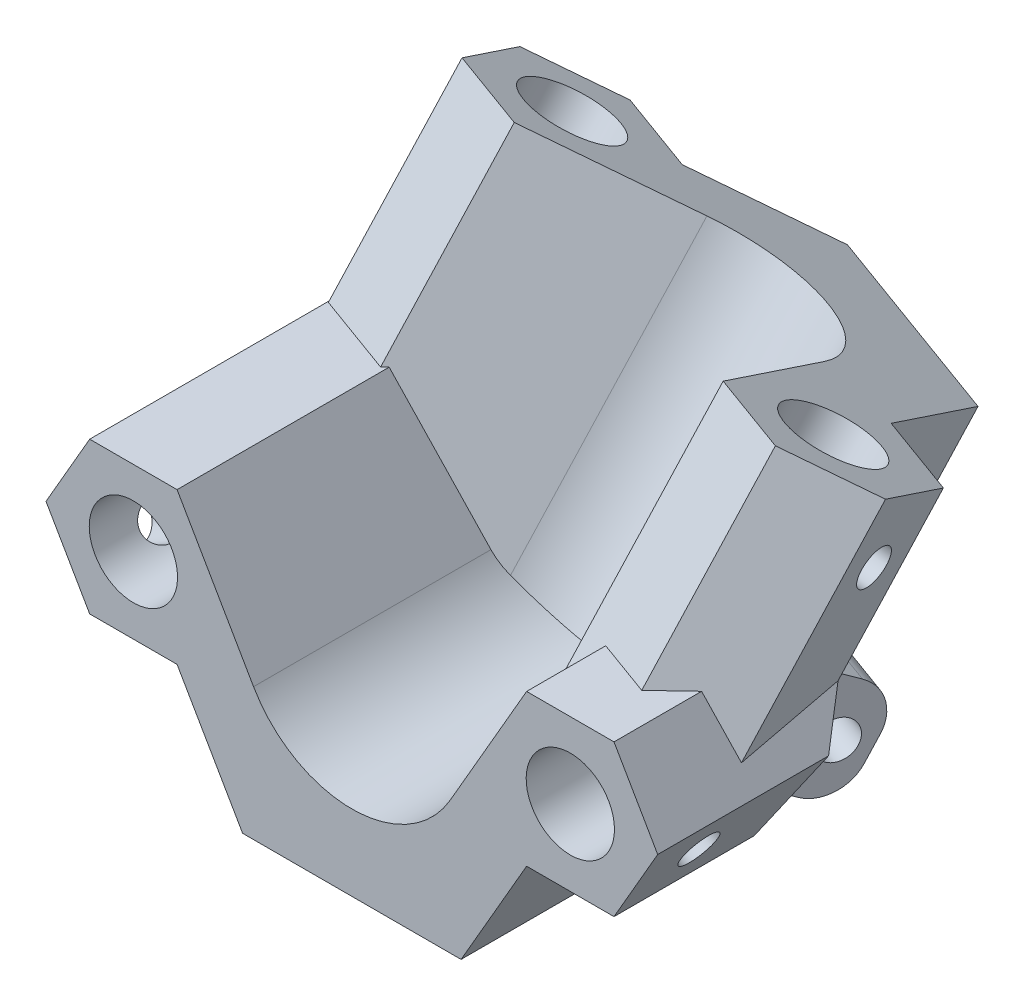
SolidWorks part; units mm, degrees
ref_plane "Front Plane" through (0, 0, 0) normal (0, 0, 1) x (1, 0, 0)
ref_plane "Top Plane" through (0, 0, 0) normal (0, 1, 0) x (1, 0, 0)
ref_plane "Right Plane" through (0, 0, 0) normal (1, 0, 0) x (0, 0, -1)
sketch "Sketch2" plane through (0, 0, 0) normal (0, 1, 0) x (1, 0, 0)
  line L0 (0, 0) -> (0, -10) construction
  line L1 (0, 0) -> (3.4202, 9.3969) construction
  dimension "D1" = 10
  dimension "D2" = 10
  dimension "D3" = 160
ref_plane "Plane1" through (0, 0, 0) normal (0.9397, 0, 0.342) x (0.342, 0, -0.9397)
sketch "Sketch3" plane through (0, 0, 0) normal (0.9397, 0, 0.342) x (0.342, 0, -0.9397)
  line L0 (0, 0) -> (10, 17.3205) construction
  line L1 (10, 17.3205) -> (10, 0) construction
  line L2 (10, 0) -> (0, 0) construction
  dimension "D1" = 30
  dimension "D2" = 10
sketch "Sketch5" plane through (0, 0, 0) normal (0, 0, 1) x (1, 0, 0)
  line L0 (0, 0) -> (10.3923, 0) construction
  line L1 (15.5705, 3.0311) -> (8.6603, 15)
  line L2 (8.6603, 15) -> (-8.6603, 15)
  line L3 (-8.6603, 15) -> (-13.8564, 6)
  line L4 (-13.8564, -6) -> (-8.6603, -15)
  line L5 (-8.6603, -15) -> (8.6603, -15)
  line L6 (8.6603, -15) -> (13.8564, -6)
  line L7 (0, -55) -> (0, 55) construction
  line L8 (24.2487, 0) -> (20.7846, 6)
  line L9 (20.7846, 6) -> (13.8564, 6)
  line L10 (13.8564, 6) -> (7.7942, -4.5)
  line L11 (10.3923, 0) -> (7.7942, 4.5) construction
  line L12 (13.8564, -6) -> (20.7846, -6)
  line L13 (20.7846, -6) -> (24.2487, 0)
  line L14 (-20.7846, -6) -> (-24.2487, 0)
  line L15 (-13.8564, -6) -> (-20.7846, -6)
  line L16 (-7.7942, 4.5) -> (-13.8564, -6) construction
  line L17 (-13.8564, 6) -> (-7.7942, -4.5)
  line L18 (-20.7846, 6) -> (-13.8564, 6)
  line L19 (-24.2487, 0) -> (-20.7846, 6)
  line L20 (-13.8564, 6) -> (-15.5705, 3.0311) construction
  line L21 (-15.5705, 3.0311) -> (-17.3205, 0) construction
  line L22 (-17.3205, 0) -> (-15.5705, -3.0311) construction
  line L23 (-15.5705, -3.0311) -> (-13.8564, -6) construction
  line L24 (-7.7942, -4.5) -> (-10.3923, 0) construction
  line L25 (-10.3923, 0) -> (-7.7942, 4.5) construction
  line L26 (12.1244, -3) -> (13.8564, -6) construction
  line L27 (13.8564, -6) -> (14.3205, -5.1962) construction
  line L28 (15.5705, -3.0311) -> (17.3205, 0) construction
  line L29 (14.3205, -5.1962) -> (15.5705, -3.0311) construction
  line L30 (7.7942, 4.5) -> (12.1244, -3) construction
  line L31 (7.7942, -4.5) -> (10.3923, 0) construction
  line L32 (10.3923, 0) -> (9, 0) construction
  line L33 (9, 0) -> (15, 0) construction
  line L34 (15, 0) -> (17.3205, 0) construction
  line L35 (17.3205, 0) -> (15.5705, 3.0311) construction
  circle A0 centre (0, 0) radius 15 construction
  arc A1 (-7.7942, -4.5) -> (7.7942, -4.5) centre (0, 0) ccw
  circle A2 centre (17.3205, 0) radius 6 construction
  circle A3 centre (17.3205, 0) radius 3.5
  circle A4 centre (-17.3205, 0) radius 3.5
  arc A5 (7.7942, -4.5) -> (-7.7942, -4.5) centre (0, 0) ccw construction
  dimension "D2" = 18
  dimension "D4" = 7
  dimension "D1" = 30
  dimension "D3" = 12
extrude "Boss-Extrude2" add sketch "Sketch5" along normal blind 15 contours A4 | L17 A1 L10 L9 L8 L13 L12 L6 L5 L4 L15 L14 L19 L18 | A3
ref_plane "Plane2" through (3.4202, 17.3205, -9.3969) normal (0.171, 0.866, -0.4698) x (0.9853, -0.1503, 0.0815)
sketch "Sketch10" plane through (0, 0, 0) normal (0, 0, -1) x (-1, 0, 0)
  line L0 (-7.7942, -4.5) -> (-13.8564, 6)
  line L1 (-13.8564, 6) -> (-20.7846, 6)
  line L2 (-20.7846, 6) -> (-24.2487, 0)
  line L3 (-24.2487, 0) -> (-20.7846, -6)
  line L4 (-20.7846, -6) -> (-13.8564, -6)
  line L5 (-13.8564, -6) -> (-8.6603, -15)
  line L6 (-8.6603, -15) -> (8.6603, -15)
  line L7 (8.6603, -15) -> (13.8564, -6)
  line L8 (13.8564, -6) -> (20.7846, -6)
  line L9 (20.7846, -6) -> (24.2487, 0)
  line L10 (24.2487, 0) -> (20.7846, 6)
  line L11 (20.7846, 6) -> (13.8564, 6)
  line L12 (20.7846, 6) -> (13.8564, 6) construction
  line L13 (13.8564, 6) -> (7.7942, -4.5)
  arc A0 (-7.7942, -4.5) -> (7.7942, -4.5) centre (0, 0) ccw
  arc A1 (-7.7942, -4.5) -> (7.7942, -4.5) centre (0, 0) ccw construction
  arc A2 (7.7942, -4.5) -> (-7.7942, -4.5) centre (0, 0) ccw construction
sketch "Sketch6" plane through (3.4202, 17.3205, -9.3969) normal (0.171, 0.866, -0.4698) x (0.9853, -0.1503, 0.0815)
  line L0 (-4.5094, -14.3061) -> (4.5094, 14.3061) construction
  line L1 (-3.7502, 16.9096) -> (-11.4117, 9.8881)
  line L2 (-15.7615, 1.79) -> (-15.0192, -1.5568)
  line L3 (-12.769, -11.7026) -> (-4.5094, -14.3061) construction
  line L4 (11.4117, -9.8881) -> (12.096, -9.2609) construction
  line L5 (15.0192, 1.5568) -> (12.769, 11.7026)
  line L6 (12.769, 11.7026) -> (-3.7502, 16.9096)
  line L7 (2.6035, 8.2596) -> (0, 0) construction
  line L8 (-14.3061, 4.5094) -> (16.5193, -5.207) construction
  line L9 (3.7502, -16.9096) -> (11.4117, -9.8881) construction
  line L10 (23.127, -7.2898) -> (21.6269, -0.526)
  line L11 (21.6269, -0.526) -> (15.0192, 1.5568)
  line L12 (15.0192, 1.5568) -> (12.4654, -0.7837) construction
  line L13 (8.7865, 1.9487) -> (11.4117, -9.8881)
  line L14 (11.4117, -9.8881) -> (18.0194, -11.9709)
  line L15 (18.0194, -11.9709) -> (23.127, -7.2898)
  line L16 (-23.127, 7.2898) -> (-21.6269, 0.526)
  line L17 (-21.6269, 0.526) -> (-15.0192, -1.5568)
  line L18 (-15.0192, -1.5568) -> (-6.0809, 6.635)
  line L19 (-10.6616, 6.5061) -> (-11.4117, 9.8881) construction
  line L20 (-11.4117, 9.8881) -> (-18.0194, 11.9709)
  line L21 (-18.0194, 11.9709) -> (-23.127, 7.2898)
  line L22 (-4.5094, -14.3061) -> (3.7502, -16.9096) construction
  line L23 (-15.0192, -1.5568) -> (-12.769, -11.7026) construction
  line L24 (-6.0809, 6.635) -> (-9.9116, 3.1242) construction
  line L25 (-9.9116, 3.1242) -> (-8.7865, -1.9487) construction
  line L26 (-8.7865, -1.9487) -> (-10.6616, 6.5061) construction
  line L27 (-11.4117, 9.8881) -> (-12.096, 9.2609) construction
  line L28 (-13.939, 7.5718) -> (-16.5193, 5.207) construction
  line L29 (-12.096, 9.2609) -> (-13.939, 7.5718) construction
  line L30 (-16.5193, 5.207) -> (-14.3061, 4.5094) construction
  line L31 (-16.5193, 5.207) -> (-15.7615, 1.79) construction
  line L32 (9.9116, -3.1242) -> (8.7865, 1.9487) construction
  line L33 (6.0809, -6.635) -> (9.9116, -3.1242) construction
  line L34 (12.4654, -0.7837) -> (6.0809, -6.635) construction
  line L35 (16.5193, -5.207) -> (15.7615, -1.79) construction
  line L36 (15.7615, -1.79) -> (15.2202, 0.6507) construction
  line L37 (15.2202, 0.6507) -> (15.0192, 1.5568) construction
  line L38 (13.939, -7.5718) -> (16.5193, -5.207) construction
  line L39 (12.096, -9.2609) -> (13.939, -7.5718) construction
  circle A0 centre (0, 0) radius 15 construction
  arc A1 (8.7865, 1.9487) -> (-6.0809, 6.635) centre (0, 0) ccw
  circle A2 centre (16.5193, -5.207) radius 6 construction
  circle A3 centre (16.5193, -5.207) radius 3.5
  circle A4 centre (-16.5193, 5.207) radius 6 construction
  circle A5 centre (-16.5193, 5.207) radius 3.5
  arc A6 (-2.7056, -8.5837) -> (8.7865, 1.9487) centre (0, 0) ccw construction
  arc A7 (-6.0809, 6.635) -> (-2.7056, -8.5837) centre (0, 0) ccw construction
  dimension "D2" = 18
  dimension "D3" = 7
  dimension "D5" = 7
  dimension "D1" = 30
  dimension "D4" = 12
  dimension "D6" = 12
extrude "Boss-Extrude3" add sketch "Sketch6" against normal up to surface (37.3205 mm away) contours L18 A1 L13 L14 L15 L10 L11 L5 L6 L1 L20 L21 L16 L17 | A5 | A3 up to face at (0, -15, 7.5)
sketch "Sketch7" plane through (0, 0, 15) normal (0, 0, 1) x (1, 0, 0)
  circle A0 centre (-17.3205, 0) radius 3.5
  circle A1 centre (-17.3205, 0) radius 3.5 construction
  circle A2 centre (0, 0) radius 9
  arc A3 (-7.7942, -4.5) -> (7.7942, -4.5) centre (0, 0) ccw construction
  circle A4 centre (17.3205, 0) radius 3.5
  arc A5 (17.0124, -3.4864) -> (15.7099, -3.1074) centre (17.3205, 0) ccw construction
extrude "Cut-Extrude1" cut sketch "Sketch7" against normal up to surface (15 mm away) up to face at (-10.0818, -3.3213, 0)
sketch "Sketch8" plane through (0, 0, 0) normal (0, 1, 0) x (1, 0, 0)
  line L0 (-24.2487, -15) -> (24.2487, -15)
  line L1 (24.2487, -15) -> (24.2487, -21.7571)
  line L2 (24.2487, -21.7571) -> (-24.2487, -21.7571)
  line L3 (-24.2487, -21.7571) -> (-24.2487, -15)
extrude "Cut-Extrude2" cut sketch "Sketch8" against normal through all both and the other way through all
sketch "Sketch9" plane through (0, 0, 15) normal (0, 0, 1) x (1, 0, 0)
  line L0 (-8.6603, -15) -> (-13.8564, -6)
  line L1 (-13.8564, -6) -> (-20.7846, -6)
  line L2 (-20.7846, -6) -> (-24.2487, 0)
  line L3 (-24.2487, 0) -> (-25.7483, -15)
  line L4 (-25.7483, -15) -> (-8.6603, -15)
  line L5 (8.6603, -15) -> (13.8564, -6)
  line L6 (13.8564, -6) -> (20.7846, -6)
  line L7 (20.7846, -6) -> (24.2487, 0)
  line L8 (24.2487, 0) -> (19.6596, -15)
  line L9 (19.6596, -15) -> (8.6603, -15)
  point P16 (0, 0)
extrude "Cut-Extrude3" cut sketch "Sketch9" against normal through all both and the other way through all
extrude "Boss-Extrude4" add sketch "Sketch10" along normal up to surface (12.8304 mm away) up to face at (6.3157, -3.7874, -13.8064)
sketch "Sketch11" plane through (3.4202, 17.3205, -9.3969) normal (0.171, 0.866, -0.4698) x (0.9853, -0.1503, 0.0815)
  line L0 (-3.7502, 16.9096) -> (-11.4117, 9.8881)
  line L1 (-11.4117, 9.8881) -> (-18.0194, 11.9709)
  line L2 (-18.0194, 11.9709) -> (-24.4549, 6.0728)
  line L3 (-22.6683, -13.1846) -> (-26.1144, 23.959) construction
  line L4 (-24.4549, 6.0728) -> (-26.1144, 23.959)
  line L5 (-26.1144, 23.959) -> (-3.7502, 16.9096)
  line L6 (12.769, 11.7026) -> (15.0192, 1.5568)
  line L7 (15.0192, 1.5568) -> (24.01, -1.2771)
  line L8 (25.1148, -13.1846) -> (23.1081, 8.4437) construction
  line L9 (24.01, -1.2771) -> (23.1081, 8.4437)
  line L10 (23.1081, 8.4437) -> (12.769, 11.7026)
extrude "Cut-Extrude4" cut sketch "Sketch11" against normal through all both and the other way through all
sketch "Sketch12" plane through (-18.1865, -10.5, 0) normal (-0.866, -0.5, 0) x (0, 0, 1)
  line L0 (15, 8.6603) -> (-7.4822, 8.6603) construction
  line L1 (15, 5.1962) -> (15, 12.1244) construction
  line L2 (-8.0554, 5.1962) -> (-6.909, 12.1244) construction
  circle A0 centre (10, 8.6603) radius 1.5
  dimension "D1" = 3
  dimension "D2" = 5
extrude "Cut-Extrude5" cut sketch "Sketch12" against normal up to surface and the other way through all up to face at (-20.8205, 0, 15)
sketch "Sketch13" plane through (18.1865, -10.5, 0) normal (0.866, -0.5, 0) x (0, 0, -1)
  line L0 (-15, 8.6603) -> (-2.6658, 8.6603) construction
  line L1 (-15, 5.1962) -> (-15, 12.1244) construction
  line L2 (-3.8786, 5.1962) -> (-1.453, 12.1244) construction
  circle A0 centre (-10, 8.6603) radius 1.5
  dimension "D1" = 3
  dimension "D2" = 5
extrude "Cut-Extrude6" cut sketch "Sketch13" against normal up to surface (2.8377 mm away) contours A0 up to face at (17.3205, 0, 0.7154)
sketch "Sketch14" plane through (20.1998, -5.25, -2.3247) normal (0.9619, -0.25, -0.1107) x (-0.1071, 0.0278, -0.9939)
  line L0 (1.8237, 21.7181) -> (-5.4703, 8.1224) construction
  line L1 (-1.2289, 23.3557) -> (4.8762, 20.0804) construction
  line L2 (-1.2869, 8.5925) -> (-9.6536, 7.6523) construction
  circle A0 centre (-0.5401, 17.3121) radius 1.5
  dimension "D1" = 3
  dimension "D2" = 5
extrude "Cut-Extrude7" cut sketch "Sketch14" against normal up to surface (2.5726 mm away) up to face at (19.6962, 18.9896, -0.3966)
sketch "Sketch15" plane through (-13.9797, -5.25, -14.765) normal (-0.6657, -0.25, -0.7031) x (-0.7462, 0.223, 0.6272)
  line L0 (3.8464, 21.4524) -> (9.4928, -2.5305) construction
  line L1 (0.4745, 20.6585) -> (7.2183, 22.2463) construction
  line L2 (9.1192, -2.9545) -> (13.7614, 2.3146) construction
  circle A0 centre (4.9923, 16.5855) radius 1.5
  dimension "D1" = 3
  dimension "D2" = 5
extrude "Cut-Extrude8" cut sketch "Sketch15" against normal up to surface (2.7674 mm away) contours A0 up to face at (-12.8558, 18.9896, -12.2445)
sketch "Sketch16" plane through (4.443, -7.5, -12.207) normal (0.2962, -0.5, -0.8138) x (-0.9551, -0.1551, -0.2524)
  line L0 (-3.5809, 19.6768) -> (1.5506, -8.5203) construction
  line L1 (-12.1012, 18.1262) -> (4.9394, 21.2274) construction
  line L2 (10.0709, -6.9697) -> (-4.4154, -9.606) construction
  line L3 (-0.909, -8.9679) -> (-2.3414, -1.0972)
  line L4 (-2.3414, -1.0972) -> (2.5778, -0.202)
  line L5 (2.5778, -0.202) -> (4.0102, -8.0727)
  line L6 (4.0102, -8.0727) -> (-0.909, -8.9679)
  point P8 (0.1182, -0.6496)
  dimension "D1" = 5
  dimension "D2" = 8
extrude "Boss-Extrude5" add sketch "Sketch16" along normal blind 10
sketch "Sketch17" plane through (2.3492, 0, 0.8551) normal (0.9397, 0, 0.342) x (0.342, 0, -0.9397)
  line L0 (19.3205, -16.5359) -> (10.6603, -11.5359) construction
  line L3 (21.3205, -13.0718) -> (17.3205, -20) construction
  line L4 (12.6603, -8.0718) -> (8.6603, -15) construction
  circle A0 centre (17.1554, -15.2859) radius 1.5
  point P8 (15.5065, -14.3339)
  dimension "D1" = 3
  dimension "D2" = 2.5
extrude "Cut-Extrude9" cut sketch "Sketch17" against normal through all
fillet "Fillet1" radius 3 1 edges at (7.292, -13.0718, -20.0347) type face fillet first side face at (5.8111, -10.5718, -15.9657) second side face at (6.608, -16.5359, -18.1553)
fillet "Fillet2" radius 3 1 edges at (5.924, -20, -16.276) type face fillet first side face at (6.3515, -17.8349, -17.4506) second side face at (4.443, -17.5, -12.207)
